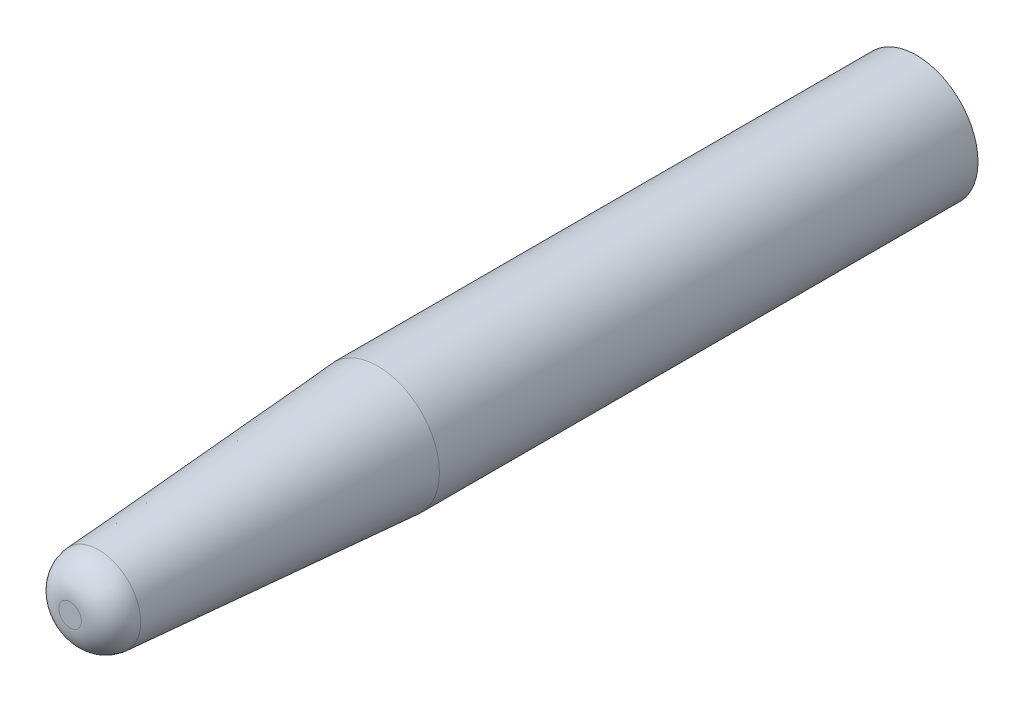
SolidWorks part; units mm, degrees
ref_plane "Front Plane" through (0, 0, 0) normal (0, 0, 1) x (1, 0, 0)
ref_plane "Top Plane" through (0, 0, 0) normal (0, 1, 0) x (1, 0, 0)
ref_plane "Right Plane" through (0, 0, 0) normal (1, 0, 0) x (0, 0, -1)
sketch "Sketch1" plane through (0, 0, 0) normal (0, 0, 1) x (1, 0, 0)
  circle A0 centre (0, 0) radius 2
  dimension "D1" = 4
extrude "Boss-Extrude1" add sketch "Sketch1" along normal blind 10 draft 4
extrude "Boss-Extrude2" add sketch "Sketch1<2>" against normal blind 17.5
sketch "Sketch1<2>" plane through (0, 0, 0) normal (0, 0, 1) x (1, 0, 0) same geometry as "Sketch1"
fillet "Fillet1" radius 1 1 edges at (1.3007, 0, 10)
